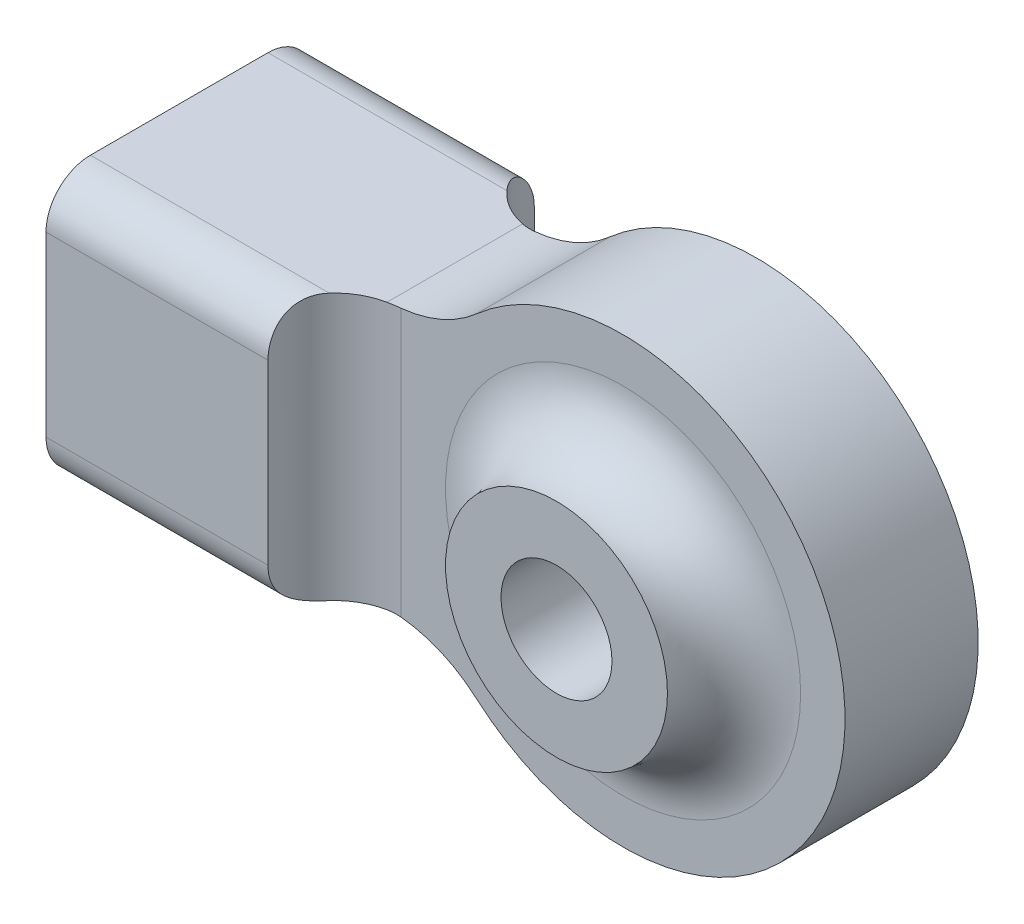
SolidWorks part; units mm, degrees
ref_plane "前视基准面" through (0, 0, 0) normal (0, 0, 1) x (1, 0, 0)
ref_plane "上视基准面" through (0, 0, 0) normal (0, 1, 0) x (1, 0, 0)
ref_plane "右视基准面" through (0, 0, 0) normal (1, 0, 0) x (0, 0, -1)
sketch "草图1" plane through (0, 0, 0) normal (0, 0, 1) x (1, 0, 0)
  line L0 (0, 0) -> (-23, 0)
  line L1 (0, 0) -> (0, -6)
  line L3 (0, -6) -> (-23, -6)
  line L4 (0, -6) -> (0, 6)
  line L5 (0, 6) -> (-23, 6)
  line L6 (-23, -6) -> (-23, 6)
  circle A0 centre (0, 0) radius 10
  dimension "D1" = 20
  dimension "D2" = 23
  dimension "D3" = 6
  dimension "D4" = 12
  dimension "D5" = 23
extrude "凸台-拉伸1" add sketch "草图1" along normal blind 6 contours A0 L0 L6 L3 | A0 L5 L6 L0 | L5 A0 L0 L4 | L0 A0 L3 L1 | L3 A0 L5 L4 L1 region at (-4.6996, -2.8957, 0) region at (2.6163, 0, 0) region at (-4.6996, 2.8957, 0) region at (-16.1687, -3.0716, 0) region at (-16.1687, 3.0716, 0)
sketch "草图2" plane through (-23, 0, 0) normal (-1, 0, 0) x (0, 0, 1)
  line L0 (0, 6) -> (6, -6)
  line L1 (0, -6) -> (6, 6)
  line L3 (9, 6) -> (-3, 6)
  line L4 (0, 6) -> (0, -6)
  line L5 (0, -6) -> (6, -6)
  line L6 (6, -6) -> (6, 6)
  line L7 (6, 6) -> (0, 6)
  line L8 (0, 6) -> (0, -6)
  line L9 (0, -6) -> (6, -6)
  line L10 (6, -6) -> (6, 6)
  line L11 (6, 6) -> (0, 6)
  line L12 (9, 6) -> (9, -6)
  line L13 (9, -6) -> (-3, -6)
  line L14 (-3, 6) -> (-3, -6)
  line L15 (9, 6) -> (-3, -6) construction
  line L16 (9, -6) -> (-3, 6) construction
  point P2 (3, 0)
  line M7 (0, 6) -> (0, -6)
  line M9 (6, -6) -> (6, 6)
  dimension "D2" = 12
  dimension "D3" = 12
  dimension "D1" = 0
extrude "凸台-拉伸2" add sketch "草图2" against normal blind 10 contours L13 L12 L3 M9 | L3 L14 L13 M7 region at (-23, 0, -1.5) region at (-23, 0, 7.5)
fillet "圆角1" radius 3 2 edges at (-13, 0, 6) (-13, 0, 0)
fillet "圆角2" radius 6 2 edges at (-8, 6, 3) (-8, -6, 3)
sketch "草图3" plane through (-23, 0, 0) normal (-1, 0, 0) x (0, 0, 1)
  line L0 (-3, 6) -> (9, -6)
  line L1 (-3, -6) -> (9, 6)
  line L4 (9, 6) -> (-3, 6)
  line L5 (-3, 6) -> (-3, -6)
  line L6 (-3, -6) -> (9, -6)
  line L7 (9, -6) -> (9, 6)
  line L8 (9, 6) -> (-3, 6)
  line L9 (-3, 6) -> (-3, -6)
  line L10 (-3, -6) -> (9, -6)
  line L11 (9, -6) -> (9, 6)
  circle A0 centre (3, 0) radius 2.5
  dimension "D2" = 5
  dimension "D1" = 0
extrude "切除-拉伸1" cut sketch "草图3" against normal blind 5 contours A0
fillet "圆角3" radius 2 4 edges at (-18, 6, 9) (-18, 6, -3) (-18, -6, -3) (-18, -6, 9)
sketch "草图4" plane through (0, 0, 0) normal (0, 0, -1) x (-1, 0, 0)
  line L1 (10, -6.0284) -> (10, 6.0284)
  line L2 (10, -6.0284) -> (10, 6.0284)
  circle A0 centre (0, 0) radius 5
  arc A3 (6.6144, 7.5) -> (6.6144, -7.5) centre (0, 0) ccw
  arc A4 (10, -6.0284) -> (6.6144, -7.5) centre (10.583, -12) ccw
  arc A5 (6.6144, 7.5) -> (10, 6.0284) centre (10.583, 12) ccw
  arc A6 (6.6144, 7.5) -> (6.6144, -7.5) centre (0, 0) ccw
  arc A7 (10, -6.0284) -> (6.6144, -7.5) centre (10.583, -12) ccw
  arc A8 (6.6144, 7.5) -> (10, 6.0284) centre (10.583, 12) ccw
  dimension "D2" = 10
  dimension "D1" = 0
extrude "凸台-拉伸3" add sketch "草图4" along normal blind 3 contours A0
sketch "草图5" plane through (0, 0, 6) normal (0, 0, 1) x (1, 0, 0)
  circle A1 centre (0, 0) radius 5
  circle A2 centre (0, 0) radius 5
  dimension "D1" = 0
extrude "凸台-拉伸4" add sketch "草图5" along normal blind 3
sketch "草图6" plane through (0, 0, -3) normal (0, 0, -1) x (-1, 0, 0)
  circle A0 centre (0, 0) radius 2.5
  dimension "D1" = 5
extrude "切除-拉伸2" cut sketch "草图6" against normal blind 20
fillet "圆角4" radius 3 2 edges at (5, 0, 0) (5, 0, 6)
